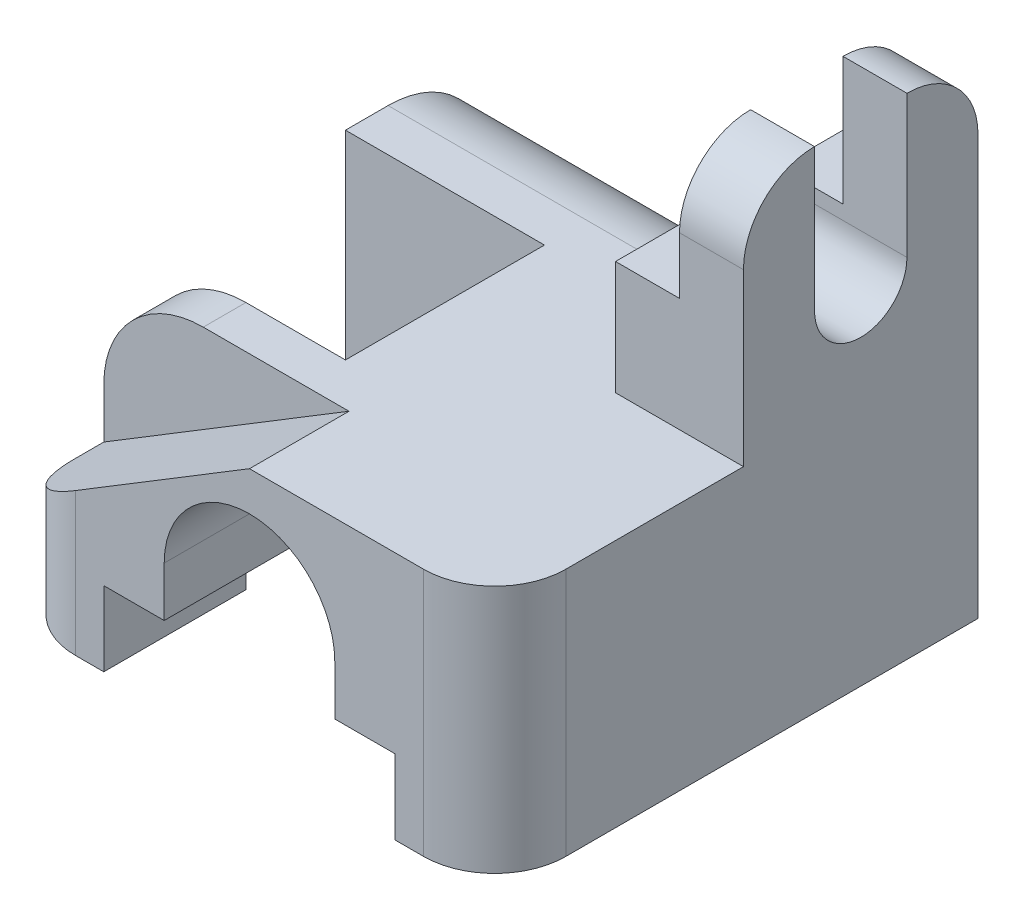
SolidWorks part; units mm, degrees
ref_plane "Front Plane" through (0, 0, 0) normal (0, 0, 1) x (1, 0, 0)
ref_plane "Top Plane" through (0, 0, 0) normal (0, 1, 0) x (1, 0, 0)
ref_plane "Right Plane" through (0, 0, 0) normal (1, 0, 0) x (0, 0, -1)
sketch "Sketch1" plane through (0, 0, 0) normal (0, 0, 1) x (1, 0, 0)
  line L1 (34.5, -17.5) -> (-34.5, -17.5)
  line L2 (34.5, -17.5) -> (34.5, 17.5)
  line L3 (34.5, 17.5) -> (-34.5, 17.5)
  line L4 (-34.5, -17.5) -> (-34.5, 17.5)
  line L5 (34.5, -17.5) -> (-34.5, 17.5) construction
  line L6 (34.5, 17.5) -> (-34.5, -17.5) construction
  point P0 (0, 0)
  dimension "D1" = 35
  dimension "D2" = 69
extrude "Boss-Extrude1" add sketch "Sketch1" against normal blind 68
sketch "Sketch2" plane through (0, 0, 0) normal (0, 0, 1) x (1, 0, 0)
  line L0 (-20.5, -17.5) -> (-20.5, -7)
  line L1 (-34.5, -17.5) -> (34.5, -17.5) construction
  line L2 (-20.5, -7) -> (-12, -7)
  line L4 (20.5, -7) -> (20.5, -17.5)
  line L5 (20.5, -17.5) -> (-20.5, -17.5)
  line L6 (0, 0) -> (0, -34.2721) construction
  line L7 (-12, 0) -> (-12, -7)
  line L8 (12, 0) -> (12, -7)
  line L9 (20.5, -7) -> (12, -7)
  arc A0 (-12, 0) -> (12, 0) centre (0, 0) cw
  dimension "D3" = 12
  dimension "D1" = 41
  dimension "D2" = 7
extrude "Cut-Extrude1" cut sketch "Sketch2" against normal through all
fillet "Fillet1" radius 10 2 edges at (34.5, 0, 0) (-34.5, 0, 0)
sketch "Sketch4" plane through (0, 0, 0) normal (0, 0, 1) x (1, 0, 0)
  line L0 (0, 17.5) -> (-34.5, -3.5)
  line L1 (24.5, 17.5) -> (-24.5, 17.5) construction
  line L2 (-34.5, -17.5) -> (-34.5, 17.5) construction
  line L3 (-34.5, -17.5) -> (-24.5, -17.5) construction
  line L4 (-34.5, -3.5) -> (-34.5, 17.5)
  line L5 (-34.5, 17.5) -> (0, 17.5)
  dimension "D1" = 14
extrude "Cut-Extrude2" cut sketch "Sketch4" against normal blind 14
ref_plane "Plane1" through (0, 0, -34) normal (0, 0, 1) x (1, 0, 0)
sketch "Sketch5" plane through (0, 0, -34) normal (0, 0, 1) x (1, 0, 0)
  line L0 (-34.5, -17.5) -> (-20.5, -17.5)
  line L1 (-34.5, -17.5) -> (-24.5, -17.5) construction
  line L2 (-20.5, -17.5) -> (-20.5, -10.5)
  line L3 (-34.5, 17.5) -> (-6.5, 17.5) construction
  line L4 (0, 17.5) -> (-34.5, 17.5) construction
  line L5 (-6.5, 17.5) -> (-6.5, 10.5)
  line L6 (-11.2399, 0) -> (-11.2399, -10.5)
  line L7 (-20.5, -10.5) -> (-11.2399, -10.5)
  line L8 (-34.5, -17.5) -> (-34.5, 17.5)
  line L9 (-34.5, 17.5) -> (-6.5, 17.5)
  arc A0 (-6.5, 10.5) -> (-11.2399, 0) centre (2.7601, 0) ccw
  dimension "D5" = 14
  dimension "D1" = 14
  dimension "D2" = 7
  dimension "D3" = 28
  dimension "D4" = 7
  dimension "D6" = 2.7601
extrude "Cut-Extrude3" cut sketch "Sketch5" against normal mid plane 28
ref_plane "Plane2" through (0, 0, -35) normal (0, 0, 1) x (1, 0, 0)
sketch "Sketch6" plane through (0, 0, -35) normal (0, 0, 1) x (1, 0, 0)
  line L0 (24.5, 17.5) -> (0, 17.5) construction
  line L1 (16.5, 17.5) -> (34.5, 17.5)
  line L2 (16.5, 17.5) -> (16.5, 33.5)
  line L3 (16.5, 33.5) -> (34.5, 33.5)
  line L4 (34.5, 17.5) -> (34.5, 33.5)
  line L5 (34.5, 17.5) -> (34.5, -17.5) construction
  dimension "D1" = 18
  dimension "D2" = 16
extrude "Boss-Extrude2" add sketch "Sketch6" against normal up to surface (33 mm away) up to face at (0, -4.25, -68)
sketch "Sketch7" plane through (16.5, 0, 0) normal (-1, 0, 0) x (0, 0, 1)
  line L0 (-58, 33.5) -> (-58, 31.5)
  line L1 (-68, 33.5) -> (-35, 33.5) construction
  line L2 (-45, 31.5) -> (-45, 33.5)
  line L3 (-58, 33.5) -> (-45, 33.5)
  line L4 (-51.5, 33.5) -> (-51.5, 17.5) construction
  line L5 (-68, 17.5) -> (-35, 17.5) construction
  line L6 (-35, 33.5) -> (-35, 17.5) construction
  arc A0 (-58, 31.5) -> (-45, 31.5) centre (-51.5, 31.5) ccw
  dimension "D3" = 6.5
  dimension "D1" = 2
  dimension "D2" = 16.5
extrude "Cut-Extrude4" cut sketch "Sketch7" against normal blind 28
fillet "Fillet3" radius 14 1 edges at (-9, 17.5, -68)
sketch "Sketch9" plane through (34.5, 0, 0) normal (1, 0, 0) x (0, 0, -1)
  line L0 (58, 33.5) -> (58, 51.5)
  line L1 (68, 41.5) -> (68, 33.5)
  line L2 (51.5, 31.5) -> (51.5, 56.4074) construction
  line L3 (58, 33.5) -> (68, 33.5)
  line L4 (45, 33.5) -> (45, 51.5)
  line L5 (35, 41.5) -> (35, 33.5)
  line L6 (45, 33.5) -> (35, 33.5)
  arc A0 (58, 51.5) -> (68, 41.5) centre (58, 41.5) cw
  arc A1 (45, 51.5) -> (35, 41.5) centre (45, 41.5) ccw
  dimension "D1" = 18
extrude "Boss-Extrude3" add sketch "Sketch9" against normal blind 9
fillet "Fillet4" radius 14 1 edges at (-34.5, 17.5, -17)
